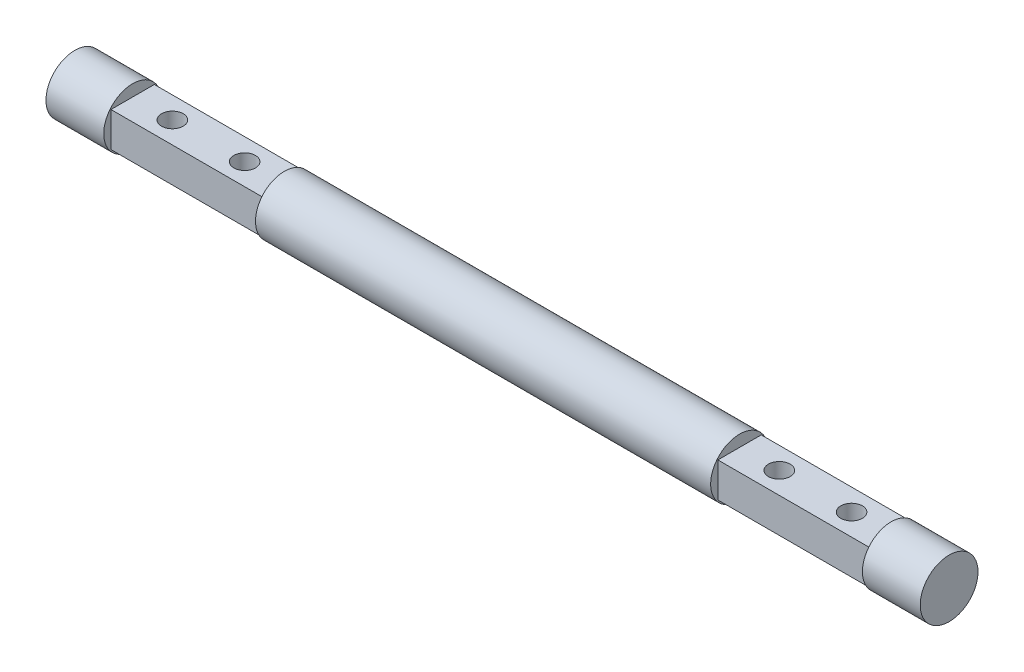
SolidWorks part; units mm, degrees
ref_plane "Front Plane" through (0, 0, 0) normal (0, 0, 1) x (1, 0, 0)
ref_plane "Top Plane" through (0, 0, 0) normal (0, 1, 0) x (1, 0, 0)
ref_plane "Right Plane" through (0, 0, 0) normal (1, 0, 0) x (0, 0, -1)
sketch "Sketch1" plane through (0, 0, 0) normal (1, 0, 0) x (0, 0, -1)
  circle A0 centre (0, 0) radius 4
  dimension "D1" = 8
extrude "Boss-Extrude1" add sketch "Sketch1" along normal blind 31.5 contours A0
sketch "Sketch2" plane through (31.5, 0, 0) normal (1, 0, 0) x (0, 0, -1)
  line L1 (3, -2.4) -> (-3, -2.4)
  line L2 (3, -2.4) -> (3, 2.4)
  line L3 (3, 2.4) -> (-3, 2.4)
  line L4 (-3, -2.4) -> (-3, 2.4)
  line L5 (3, -2.4) -> (-3, 2.4) construction
  line L6 (3, 2.4) -> (-3, -2.4) construction
  point P0 (0, 0)
  dimension "D1" = 4.8
  dimension "D2" = 6
extrude "Boss-Extrude2" add sketch "Sketch2" along normal blind 21
sketch "Sketch3" plane through (52.5, 0, 0) normal (1, 0, 0) x (0, 0, -1)
  circle A0 centre (0, 0) radius 4
  dimension "D1" = 8
extrude "Boss-Extrude3" add sketch "Sketch3" along normal blind 8
mirror "Mirror1" about plane through (0, 0, 0) normal (1, 0, 0) of "Boss-Extrude1", "Boss-Extrude2", "Boss-Extrude3"
sketch "Sketch4" plane through (0, 2.4, 0) normal (0, 1, 0) x (1, 0, 0)
  line L0 (-42, 0) -> (42, 0) construction
  line L1 (-42, 0) -> (-37, 0) construction
  line L2 (-42, 0) -> (-47, 0) construction
  line L3 (0, -4.4) -> (0, 4.4) construction
  circle A0 centre (-47, 0) radius 1.5
  circle A1 centre (-37, 0) radius 1.5
  circle A2 centre (47, 0) radius 1.5
  circle A3 centre (37, 0) radius 1.5
  dimension "D3" = 3
  dimension "D4" = 3
  dimension "D1" = 74
  dimension "D2" = 5
  dimension "D5" = 5
extrude "Cut-Extrude1" cut sketch "Sketch4" against normal through all
ref_plane "Plane1" through (0, 0, 0) normal (0, 1, 0) x (1, 0, 0)
ref_plane "Plane2" through (0, 0, 0) normal (0, 0, 1) x (1, 0, 0)
ref_point "Point12"
ref_axis "Axis4" through (-42, 2.4, 0) along (0, 1, 0)
ref_point "Point14"
ref_point "Point16"
ref_axis "Axis5" through (42, 2.4, 0) along (0, 1, 0)
ref_point "Point18"
